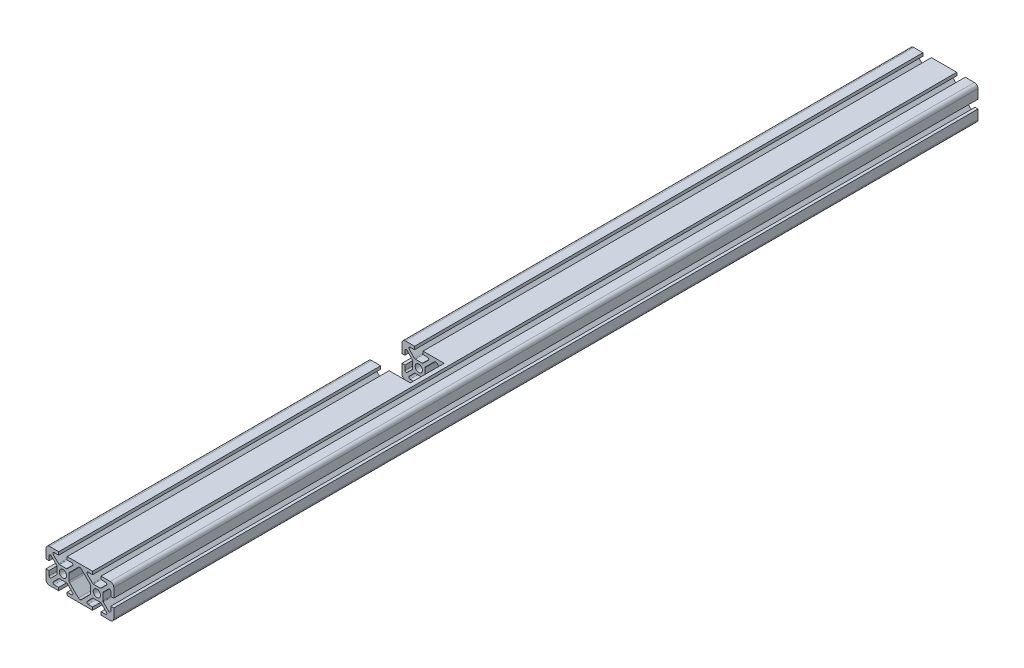
SolidWorks part; units mm, degrees
ref_plane "Front Plane" through (0, 0, 0) normal (0, 0, 1) x (1, 0, 0)
ref_plane "Top Plane" through (0, 0, 0) normal (0, 1, 0) x (1, 0, 0)
ref_plane "Right Plane" through (0, 0, 0) normal (1, 0, 0) x (0, 0, -1)
sketch "Sketch1" plane through (0, 0, 0) normal (0, 0, 1) x (1, 0, 0)
  line L0 (10, 10) -> (10, -10) construction
  line L1 (-20, 0) -> (20, 0) construction
  line L2 (12.5, -10) -> (20, -10)
  line L3 (20, -10) -> (20, -2.5)
  line L4 (12.5, -10) -> (12.5, -8.2134)
  line L5 (12.5, -8.2134) -> (16.95, -8.2134)
  line L6 (16.95, -8.2134) -> (12.3366, -3.6)
  line L7 (10, 0) -> (20, -10) construction
  line L8 (20, -2.5) -> (18.2134, -2.5)
  line L9 (18.2134, -2.5) -> (18.2134, -6.95)
  line L10 (18.2134, -6.95) -> (13.6, -2.3366)
  line L11 (15.9067, -4.6433) -> (14.6433, -5.9067) construction
  line L12 (0, 10) -> (0, -10) construction
  line L13 (0, -10) -> (-20, -10) construction
  line L14 (-10, 10) -> (10, 10) construction
  line L15 (20, 2.5) -> (20, -2.5) construction
  circle A0 centre (10, 0) radius 2.15
  arc A1 (15.5015, -8.2134) -> (15.9257, -7.1891) centre (15.5015, -7.6134) ccw construction
  point P8 (10, -3.6)
  point P16 (15.275, -5.275)
  point P30 (20, 0)
  dimension "Center Hole Diameter" = 4.3
  dimension "D3" = 0.6
  dimension "Rail Width" = 20
  dimension "T-Slot Width" = 5
  dimension "Slot Depth" = 6.4
  dimension "Rail Height" = 40
  dimension "Inner Slot Width" = 13.9
  dimension "Hole Spacing" = 20
sketch "Sketch2" plane through (0, 0, 0) normal (1, 0, 0) x (0, 0, -1)
  line L0 (-1524, -10) -> (1524, -10) construction
  line L1 (-1484, 0) -> (1484, 0) construction
  point P6 (-1484, 0)
  point P8 (1484, 0)
  dimension "Length" = 3048
  dimension "D1" = 40
sketch "Sketch3" plane through (0, 0, 0) normal (0, 0, 1) x (1, 0, 0)
  line L0 (12.5, -10) -> (17.9, -10)
  line L1 (12.5, -10) -> (20, -10) construction
  line L2 (12.5, -10) -> (12.5, -8.2134) construction
  line L3 (12.5, -8.2134) -> (16.95, -8.2134) construction
  line L4 (12.5, -8.2134) -> (12.5, -10)
  line L5 (12.5, -8.2134) -> (16.95, -8.2134)
  line L6 (10, -3.6) -> (12.3366, -3.6)
  line L7 (16.95, -8.2134) -> (12.3366, -3.6) construction
  line L8 (12.3366, -3.6) -> (16.95, -8.2134)
  line L9 (20, -10) -> (20, -2.5) construction
  line L10 (18.2134, -6.95) -> (13.6, -2.3366) construction
  line L11 (18.2134, -2.5) -> (18.2134, -6.95) construction
  line L12 (18.2134, -6.95) -> (18.2134, -2.5)
  line L13 (20, -2.5) -> (18.2134, -2.5) construction
  line L14 (18.2134, -2.5) -> (20, -2.5)
  line L15 (20, -2.5) -> (20, -7.9)
  line L16 (18.2134, -6.95) -> (13.6, -2.3366)
  line L17 (13.6, 0) -> (13.6, -2.3366)
  line L18 (-20, 0) -> (20, 0) construction
  line L19 (10, -3.6) -> (10, -2.15)
  line L20 (10, 10) -> (10, -10) construction
  line L21 (13.6, 0) -> (12.15, 0)
  arc A5 (17.9, -10) -> (20, -7.9) centre (17.9, -7.9) ccw
  circle A10 centre (10, 0) radius 2.15 construction
  arc A11 (10, -2.15) -> (12.15, 0) centre (10, 0) ccw
  dimension "D1" = 2.1
extrude "Boss-Extrude1" add sketch "Sketch3" along normal mid plane 3048
sketch "Sketch4" plane through (0, 0, 0) normal (0, 0, 1) x (1, 0, 0)
  line L0 (10, -3.6) -> (7.6634, -3.6)
  line L4 (7.6634, -3.6) -> (3.05, -8.2134)
  line L5 (3.05, -8.2134) -> (7.5, -8.2134)
  line L6 (7.5, -8.2134) -> (7.5, -10)
  line L18 (7.5, -10) -> (0, -10)
  line L19 (12.5, -10) -> (12.5, -8.2134) construction
  line L20 (12.5, -8.2134) -> (16.95, -8.2134) construction
  line L21 (10, -3.6) -> (12.3366, -3.6) construction
  line L22 (16.95, -8.2134) -> (12.3366, -3.6) construction
  line L23 (0, -8.7366) -> (6.4, -2.3366)
  line L24 (0, 10) -> (0, -10) construction
  line L25 (6.4, -2.3366) -> (6.4, 0)
  line L26 (-20, 0) -> (20, 0) construction
  line L27 (6.4, 0) -> (7.85, 0)
  line L28 (13.6, 0) -> (12.15, 0) construction
  line L29 (0, -8.7366) -> (0, -10)
  line L30 (10, -2.15) -> (10, -3.6)
  circle A4 centre (10, 0) radius 2.15 construction
  arc A5 (7.85, 0) -> (10, -2.15) centre (10, 0) ccw
extrude "Boss-Extrude2" add sketch "Sketch4" along normal mid plane 3048
mirror "Mirror1" about plane through (0, 0, 0) normal (1, 0, 0) of bodies 137 134
mirror "Mirror2" about plane through (0, 0, 0) normal (0, 1, 0) of bodies 135
fillet "Fillet1" radius 0.75 24 edges at (-7.6634, -3.6, 0) (-12.3366, -3.6, 0) (12.3366, -3.6, 0) (7.6634, -3.6, 0) (-3.05, -8.2134, 0) (-18.2134, -6.95, 0) (-16.95, -8.2134, 0) (-13.6, -2.3366, 0) (-18.2134, 6.95, 0) (-16.95, 8.2134, 0) (-12.3366, 3.6, 0) (-7.6634, 3.6, 0) (-13.6, 2.3366, 0) (-3.05, 8.2134, 0) (3.05, 8.2134, 0) (13.6, -2.3366, 0) (13.6, 2.3366, 0) (7.6634, 3.6, 0) (12.3366, 3.6, 0) (18.2134, 6.95, 0) (16.95, 8.2134, 0) (18.2134, -6.95, 0) (16.95, -8.2134, 0) (3.05, -8.2134, 0)
fillet "Fillet2" radius 1.25 6 edges at (0, -8.7366, 0) (-6.4, -2.3366, 0) (-6.4, 2.3366, 0) (6.4, -2.3366, 0) (6.4, 2.3366, 0) (0, 8.7366, 0)
sketch "Sketch5" plane through (-20, 0, 0) normal (-1, 0, 0) x (0, 0, 1)
  line L0 (1524, -10) -> (-1524, -10) construction
  line L1 (1524, 10) -> (-1014, 10)
  line L2 (1524, 10) -> (1524, -10)
  line L3 (1524, -10) -> (-1014, -10)
  line L4 (-1014, 10) -> (-1014, -10)
  line L5 (-1524, 7.9) -> (-1524, 2.5) construction
  dimension "D1" = 510
extrude "Cut-Extrude1" cut sketch "Sketch5" against normal through all
sketch "Sketch6" plane through (0, 10, 0) normal (0, 1, 0) x (1, 0, 0)
  line L0 (-20, 1014) -> (-20, 1524) construction
  line L1 (-20, 1224) -> (5, 1224)
  line L2 (-20, 1224) -> (-20, 1204)
  line L3 (-20, 1204) -> (5, 1204)
  line L4 (5, 1224) -> (5, 1204)
  line L5 (-7.5, 1524) -> (7.5, 1524) construction
  dimension "D1" = 320
  dimension "D2" = 20
  dimension "D3" = 25
extrude "Cut-Extrude2" cut sketch "Sketch6" against normal blind 40
equation "\"D1@Sketch3\" = \"D3@Sketch1\" * 3.5"
equation "\"D1@Boss-Extrude1\" = \"Length@Sketch2\""
equation "\"D1@Boss-Extrude2\" = \"Length@Sketch2\""
equation "\"D1@Sketch2\"=\"Rail Height@Sketch1\""
